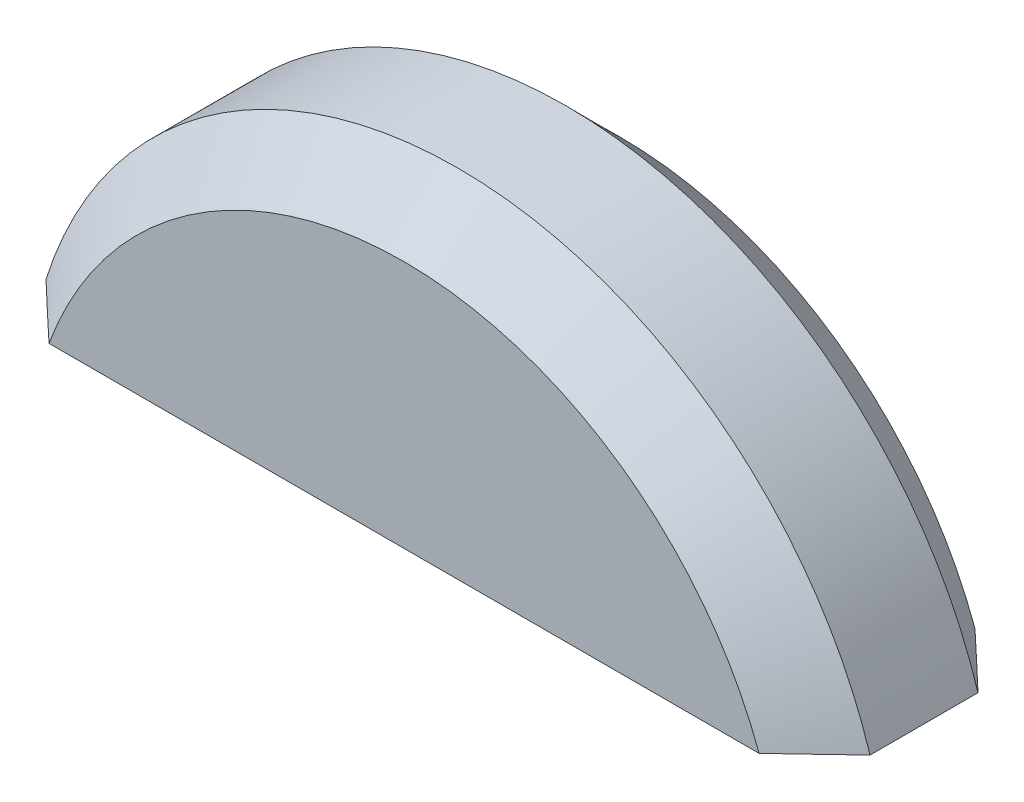
SolidWorks part; units mm, degrees
ref_plane "front" through (0, 0, 0) normal (0, 0, 1) x (1, 0, 0)
ref_plane "top" through (0, 0, 0) normal (0, 1, 0) x (1, 0, 0)
ref_plane "right" through (0, 0, 0) normal (1, 0, 0) x (0, 0, -1)
sketch "body" plane through (0, 0, 0) normal (0, 0, 1) x (1, 0, 0)
  line L0 (-1.9079, 0.6) -> (1.9079, 0.6)
  arc A0 (-1.9079, 0.6) -> (1.9079, 0.6) centre (0, 0) cw
  dimension "Diameter" = 4
  dimension "Height" = 1.4
extrude "Extrude1" add sketch "body" along normal blind 1
chamfer "Chamfer1" distance 0.25 2 edges at (0, 2, 1) (0, 2, 0)
